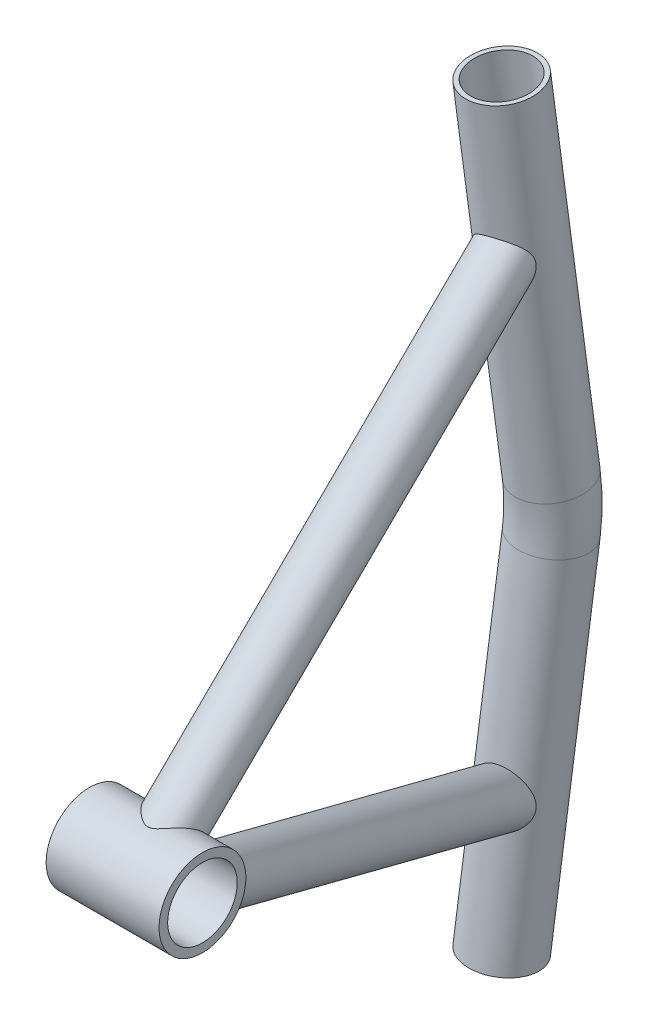
SolidWorks part; units mm, degrees
material "AISI 4130 Steel, normalized at 870C"
ref_plane "X-Y Datum" through (0, 0, 0) normal (0, 0, 1) x (1, 0, 0)
ref_plane "X-Z Datum" through (0, 0, 0) normal (0, 1, 0) x (1, 0, 0)
ref_plane "Y-Z Datum" through (0, 0, 0) normal (1, 0, 0) x (0, 0, -1)
ref_plane "FRH Reference" through (-89.8073, 0, -36.2845) normal (0.9272, 0, 0.3746) x (0.3746, 0, -0.9272)
sketch "Sketch6" plane through (0, 0, 0) normal (0, 1, 0) x (1, 0, 0)
  line L1 (20.6375, 15.875) -> (-20.6375, 15.875)
  line L2 (20.6375, 15.875) -> (20.6375, 12.7254)
  line L3 (20.6375, 12.7254) -> (-20.6375, 12.7254)
  line L4 (-20.6375, 15.875) -> (-20.6375, 12.7254)
  line L9 (-66.7868, 0) -> (90.4215, 0) construction
revolve "Revolve2" add sketch "Sketch6" angle 360 about L9
sketch3d "3DSketch2"
  line L0 (0, 0, 0) -> (0, 11.2253, -11.2253) construction
  line L1 (-66.7868, 0, 0) -> (90.4215, 0, 0) construction
  line L2 (0, 0, 0) -> (0, 0, 15.875) construction
  line L3 (0, 0, 0) -> (0, 0, -15.875) construction
  line L4 (0, 0, 0) -> (0, -11.2253, -11.2253) construction
  line L7 (20.6375, 0, -15.875) -> (-20.6375, 0, -15.875) construction
  line L8 (0, 11.2253, -11.2253) -> (-45.6789, 89.2363, -182.5965)
  line L9 (0, -11.2253, -11.2253) -> (-45.6789, -89.2363, -182.5965)
  line L10 (-47.9371, 138.4715, -177.9436) -> (-42.012, 9.2876, -190.1521)
  line L11 (-42.012, -9.2876, -190.1521) -> (-47.9371, -138.4715, -177.9436)
  line L12 (0, 0, 0) -> (86.995, 0, 0) construction
  arc A0 (-42.012, 9.2876, -190.1521) -> (-42.012, -9.2876, -190.1521) centre (-80.6149, 0, -110.6111) ccw
  point P20 (-160.5935, 0, -149.4264)
  dimension "D1" = 45
  dimension "D2" = 135
  dimension "D3" = 45
  dimension "D4" = 135
  dimension "D5" = 193.7534
  dimension "D7" = 47.485
  dimension "D6" = 155.523
  dimension "D8" = 86.995
ref_plane "Plane1" through (-45.6789, 89.2363, -182.5965) normal (-0.2358, 0.4026, -0.8845) x (-0.9718, -0.0977, 0.2146)
sketch "Sketch10" plane through (-45.6789, 89.2363, -182.5965) normal (-0.2358, 0.4026, -0.8845) x (-0.9718, -0.0977, 0.2146)
  circle A0 centre (0, 0) radius 9.525
  circle A1 centre (0, 0) radius 7.874
  dimension "D1" = 19.05
  dimension "D2" = 1.651
extrude "Boss-Extrude1" add sketch "Sketch10" against normal up to surface (203.9812 mm away) separate body up to face at (-20.6375, 0, 15.875)
ref_plane "Plane2" through (-45.6789, -89.2363, -182.5965) normal (-0.2358, -0.4026, -0.8845) x (-0.9718, 0.0977, 0.2146)
sketch "Sketch11" plane through (-45.6789, -89.2363, -182.5965) normal (-0.2358, -0.4026, -0.8845) x (-0.9718, 0.0977, 0.2146)
  circle A0 centre (0, 0) radius 9.525
  circle A1 centre (0, 0) radius 7.874
  dimension "D1" = 19.05
  dimension "D2" = 1.651
extrude "Boss-Extrude2" add sketch "Sketch11" against normal up to surface (193.2326 mm away) separate body up to face at (-20.6375, 0, 15.875)
ref_plane "Plane3" through (-47.9371, -138.4715, -177.9436) normal (-0.0456, -0.9945, 0.094) x (-0.999, 0.0454, -0.0043)
sketch "Sketch12" plane through (-47.9371, -138.4715, -177.9436) normal (-0.0456, -0.9945, 0.094) x (-0.999, 0.0454, -0.0043)
  circle A0 centre (0, 0) radius 12.7
  dimension "D1" = 25.4
sweep "Cut-Sweep1" cut profiles "Sketch12" path "3DSketch2"
ref_plane "Plane4" through (-108.6951, 0, -52.752) normal (0.8996, 0, 0.4366) x (0.4366, 0, -0.8996)
sketch "Sketch14" plane through (-108.6951, 0, -52.752) normal (0.8996, 0, 0.4366) x (0.4366, 0, -0.8996)
  line L0 (139.1563, 138.4715) -> (152.7267, 9.2876)
  line L1 (152.7267, -9.2876) -> (139.1563, -138.4715)
  arc A0 (152.7267, 9.2876) -> (152.7267, -9.2876) centre (64.3131, 0) cw
sketch "Sketch15" plane through (-47.9371, -138.4715, -177.9436) normal (-0.0456, -0.9945, 0.094) x (-0.999, 0.0454, -0.0043)
  circle A0 centre (0, 0) radius 12.7
  circle A1 centre (0, 0) radius 11.049
  dimension "D1" = 25.4
  dimension "D2" = 1.651
sweep "Sweep2" add profiles "Sketch15" path "Sketch14"
equation "\"Tube_Thickness\"=0.75"
equation "\"Wall_Thickness\"=0.065"
